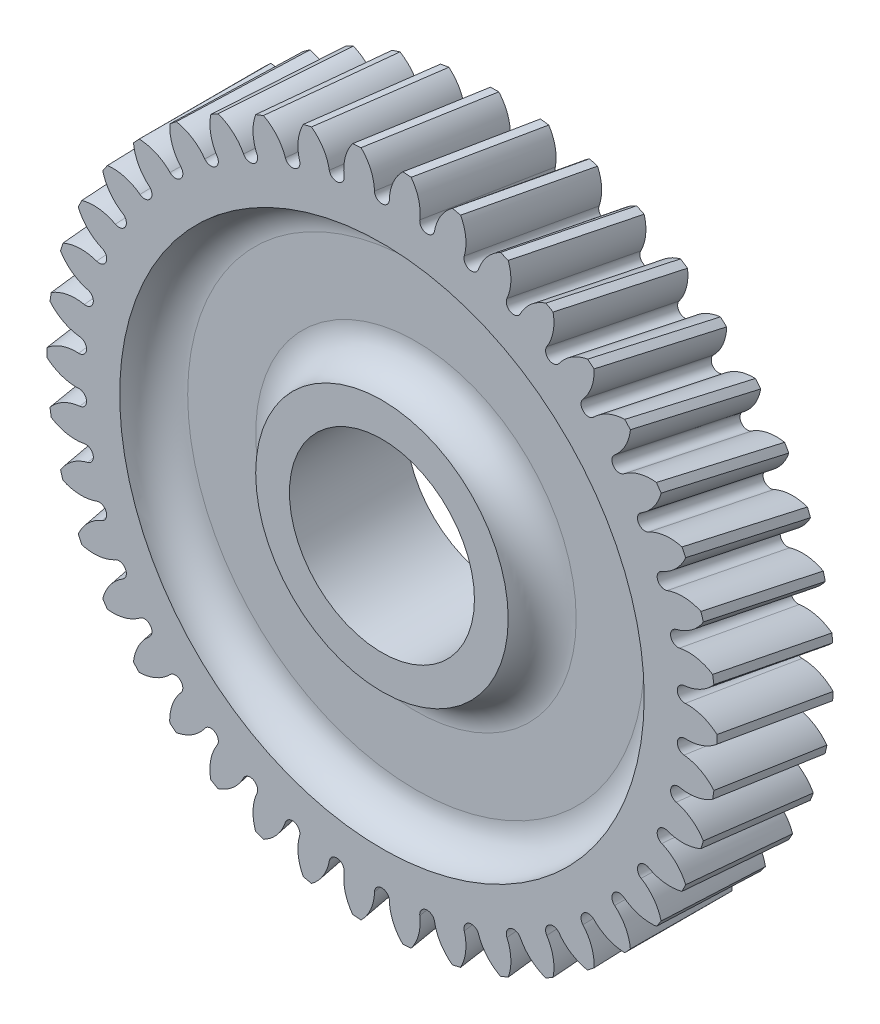
SolidWorks part; units mm, degrees
material "S355JR"
ref_plane "Front" through (0, 0, 0) normal (0, 0, 1) x (1, 0, 0)
ref_plane "Top" through (0, 0, 0) normal (0, 1, 0) x (1, 0, 0)
ref_plane "Right" through (0, 0, 0) normal (1, 0, 0) x (0, 0, -1)
sketch "Sketch1" plane through (0, 0, 0) normal (1, 0, 0) x (0, 0, -1)
  line L0 (6, 9.525) -> (-6, 9.525)
  line L1 (-6, 9.525) -> (-6, 13)
  line L2 (-2.5, 16.5) -> (-2.5, 23.5)
  line L3 (-6, 27) -> (-6, 34.5)
  line L4 (-6, 34.5) -> (6, 34.5)
  line L5 (0, 34.5) -> (0, 9.525) construction
  line L6 (6, 27) -> (6, 34.5)
  line L7 (2.5, 16.5) -> (2.5, 23.5)
  line L8 (6, 9.525) -> (6, 13)
  line L9 (0, 0) -> (28149.981, 0) construction
  arc A0 (-6, 13) -> (-2.5, 16.5) centre (-6, 16.5) ccw
  arc A1 (-2.5, 23.5) -> (-6, 27) centre (-6, 23.5) ccw
  arc A2 (2.5, 23.5) -> (6, 27) centre (6, 23.5) cw
  arc A3 (6, 13) -> (2.5, 16.5) centre (6, 16.5) cw
  dimension "D1" = 19.05
  dimension "D2" = 69
  dimension "D3" = 54
  dimension "D4" = 26
  dimension "D5" = 12
  dimension "D6" = 3.5
revolve "Revolve1" add sketch "Sketch1" angle 360 about L9
sketch "Sketch2" plane through (0, 0, 6) normal (0, 0, 1) x (1, 0, 0)
  line L0 (0, 0) -> (0, 48.7795) construction
  line L1 (-0.75, 30.4908) -> (0, 0) construction
  line L2 (-0.7687, 31.25) -> (-0.75, 30.4908) construction
  arc A0 (0.75, 30.4908) -> (-0.75, 30.4908) centre (0, 0) ccw construction
  circle A1 centre (0, 0) radius 34.5 construction
  arc A2 (2.15, 34.4329) -> (-2.15, 34.4329) centre (0, 0) ccw
  arc A6 (2.15, 34.4329) -> (0.7687, 31.25) centre (5.3884, 31.1364) ccw
  arc A7 (-0.7687, 31.25) -> (0.7687, 31.25) centre (0, 31.2689) ccw
  arc A8 (-2.15, 34.4329) -> (-0.7687, 31.25) centre (-5.3884, 31.1364) cw
  arc A9 (7.2579, 33.7279) -> (3.006, 34.3688) centre (0, 0) ccw construction
  arc A10 (7.2579, 33.7279) -> (5.4177, 30.7864) centre (9.9688, 29.9855) ccw construction
  arc A11 (3.8975, 31.0155) -> (5.4177, 30.7864) centre (4.6604, 30.9197) ccw construction
  arc A12 (3.006, 34.3688) -> (3.8975, 31.0155) centre (-0.6875, 31.5917) cw construction
  arc A13 (5.286, 30.0384) -> (3.8028, 30.262) centre (0, 0) ccw construction
  arc A14 (3.8975, 31.0155) -> (3.8028, 30.262) centre (0.6974, 31.0349) cw construction
  arc A15 (5.4177, 30.7864) -> (5.286, 30.0384) centre (7.5704, 30.022) ccw construction
  arc A16 (12.2038, 32.2695) -> (8.0948, 33.5369) centre (0, 0) ccw construction
  arc A17 (12.2038, 32.2695) -> (9.9456, 29.6351) centre (14.3266, 28.1648) ccw construction
  arc A18 (8.4766, 30.0882) -> (9.9456, 29.6351) centre (9.2167, 29.8797) ccw construction
  arc A19 (8.0948, 33.5369) -> (8.4766, 30.0882) centre (4.0286, 31.3413) cw construction
  arc A20 (9.704, 28.9151) -> (8.2706, 29.3572) centre (0, 0) ccw construction
  arc A21 (8.4766, 30.0882) -> (8.2706, 29.3572) centre (5.3152, 30.5844) cw construction
  arc A22 (9.9456, 29.6351) -> (9.704, 28.9151) centre (11.9604, 28.5584) ccw construction
  arc A23 (16.877, 30.0902) -> (13.0028, 31.9559) centre (0, 0) ccw construction
  arc A24 (16.877, 30.0902) -> (14.2514, 27.8218) centre (18.3643, 25.715) ccw construction
  arc A25 (12.8663, 28.4888) -> (14.2514, 27.8218) centre (13.5671, 28.1723) ccw construction
  arc A26 (13.0028, 31.9559) -> (12.8663, 28.4888) centre (8.6548, 30.3908) cw construction
  arc A27 (13.9052, 27.1458) -> (12.5537, 27.7967) centre (0, 0) ccw construction
  arc A28 (12.8663, 28.4888) -> (12.5537, 27.7967) centre (9.8142, 29.4506) cw construction
  arc A29 (14.2514, 27.8218) -> (13.9052, 27.1458) centre (16.0832, 26.4568) ccw construction
  arc A30 (21.1732, 27.2387) -> (17.6204, 29.661) centre (0, 0) ccw construction
  arc A31 (21.1732, 27.2387) -> (18.2389, 25.387) centre (21.9918, 22.6907) ccw construction
  arc A32 (16.9686, 26.253) -> (18.2389, 25.387) centre (17.6144, 25.8356) ccw construction
  arc A33 (17.6204, 29.661) -> (16.9686, 26.253) centre (13.0877, 28.7614) cw construction
  arc A34 (17.7957, 24.7702) -> (16.5564, 25.6152) centre (0, 0) ccw construction
  arc A35 (16.9686, 26.253) -> (16.5564, 25.6152) centre (14.0939, 27.6589) cw construction
  arc A36 (18.2389, 25.387) -> (17.7957, 24.7702) centre (19.8467, 23.7642) ccw construction
  arc A37 (24.9964, 23.7788) -> (21.8443, 26.7035) centre (0, 0) ccw construction
  arc A38 (24.9964, 23.7788) -> (21.8189, 22.385) centre (25.1281, 19.1596) ccw construction
  arc A39 (20.6919, 23.4307) -> (21.8189, 22.385) centre (21.2683, 22.9217) ccw construction
  arc A40 (21.8443, 26.7035) -> (20.6919, 23.4307) centre (17.2282, 26.4896) cw construction
  arc A41 (21.2888, 21.8412) -> (20.1892, 22.8615) centre (0, 0) ccw construction
  arc A42 (20.6919, 23.4307) -> (20.1892, 22.8615) centre (18.0589, 25.2494) cw construction
  arc A43 (21.8189, 22.385) -> (21.2888, 21.8412) centre (23.1669, 20.5408) ccw construction
  arc A44 (28.2613, 19.7877) -> (25.5803, 23.1495) centre (0, 0) ccw construction
  arc A45 (28.2613, 19.7877) -> (24.9115, 18.8831) centre (27.703, 15.2004) ccw construction
  arc A46 (23.953, 20.085) -> (24.9115, 18.8831) centre (24.447, 19.4958) ccw construction
  arc A47 (25.5803, 23.1495) -> (23.953, 20.085) centre (20.9838, 23.626) cw construction
  arc A48 (24.3063, 18.4243) -> (23.371, 19.5971) centre (0, 0) ccw construction
  arc A49 (23.953, 20.085) -> (23.371, 19.5971) centre (21.6204, 22.2758) cw construction
  arc A50 (24.9115, 18.8831) -> (24.3063, 18.4243) centre (25.9696, 16.8585) ccw construction
  arc A51 (30.8948, 15.3545) -> (28.7448, 19.0784) centre (0, 0) ccw construction
  arc A52 (30.8948, 15.3545) -> (27.4476, 14.9593) centre (29.6591, 10.9017) ccw construction
  arc A53 (26.679, 16.2907) -> (27.4476, 14.9593) centre (27.0797, 15.6345) ccw construction
  arc A54 (28.7448, 19.0784) -> (26.679, 16.2907) centre (24.2707, 20.2346) cw construction
  arc A55 (26.7808, 14.5959) -> (26.0308, 15.8949) centre (0, 0) ccw construction
  arc A56 (26.679, 16.2907) -> (26.0308, 15.8949) centre (24.6989, 18.8047) cw construction
  arc A57 (27.4476, 14.9593) -> (26.7808, 14.5959) centre (28.1922, 12.7997) ccw construction
  arc A58 (32.8382, 10.5784) -> (31.2672, 14.5811) centre (0, 0) ccw construction
  arc A59 (32.8382, 10.5784) -> (29.3706, 10.7014) centre (30.9526, 6.3595) ccw construction
  arc A60 (28.809, 12.1324) -> (29.3706, 10.7014) centre (29.1074, 11.4238) ccw construction
  arc A61 (31.2672, 14.5811) -> (28.809, 12.1324) centre (27.0154, 16.3913) cw construction
  arc A62 (28.6571, 10.4414) -> (28.1091, 11.8377) centre (0, 0) ccw construction
  arc A63 (28.809, 12.1324) -> (28.1091, 11.8377) centre (27.2258, 14.9135) cw construction
  arc A64 (29.3706, 10.7014) -> (28.6571, 10.4414) centre (29.785, 8.4549) ccw construction
  arc A65 (34.0481, 5.566) -> (33.0912, 9.7581) centre (0, 0) ccw construction
  arc A66 (34.0481, 5.566) -> (30.6375, 6.2044) centre (31.5547, 1.6752) ccw construction
  arc A67 (30.2955, 7.7032) -> (30.6375, 6.2044) centre (30.4849, 6.958) ccw construction
  arc A68 (33.0912, 9.7581) -> (30.2955, 7.7032) centre (29.1567, 12.1817) cw construction
  arc A69 (29.8932, 6.0536) -> (29.5594, 7.516) centre (0, 0) ccw construction
  arc A70 (30.2955, 7.7032) -> (29.5594, 7.516) centre (29.1444, 10.6891) cw construction
  arc A71 (30.6375, 6.2044) -> (29.8932, 6.0536) centre (30.7125, 3.9212) ccw construction
  arc A72 (34.4973, 0.4292) -> (34.176, 4.7172) centre (0, 0) ccw construction
  arc A73 (34.4973, 0.4292) -> (31.2201, 1.5688) centre (31.452, -3.0465) ccw construction
  arc A74 (31.1052, 3.1018) -> (31.2201, 1.5688) centre (31.1815, 2.3367) ccw construction
  arc A75 (34.176, 4.7172) -> (31.1052, 3.1018) centre (30.6466, 7.7001) cw construction
  arc A76 (30.4616, 1.5307) -> (30.3495, 3.0265) centre (0, 0) ccw construction
  arc A77 (31.1052, 3.1018) -> (30.3495, 3.0265) centre (30.412, 6.226) cw construction
  arc A78 (31.2201, 1.5688) -> (30.4616, 1.5307) centre (30.9539, -0.7) ccw construction
  arc A79 (34.176, -4.7172) -> (34.4973, -0.4292) centre (0, 0) ccw construction
  arc A80 (34.176, -4.7172) -> (31.1052, -3.1018) centre (30.6466, -7.7001) ccw construction
  arc A81 (31.2201, -1.5688) -> (31.1052, -3.1018) centre (31.1815, -2.3367) ccw construction
  arc A82 (34.4973, -0.4292) -> (31.2201, -1.5688) centre (31.452, 3.0465) cw construction
  arc A83 (30.3495, -3.0265) -> (30.4616, -1.5307) centre (0, 0) ccw construction
  arc A84 (31.2201, -1.5688) -> (30.4616, -1.5307) centre (31.0003, 1.6238) cw construction
  arc A85 (31.1052, -3.1018) -> (30.3495, -3.0265) centre (30.5038, -5.3057) ccw construction
  arc A86 (33.0912, -9.7581) -> (34.0481, -5.566) centre (0, 0) ccw construction
  arc A87 (33.0912, -9.7581) -> (30.2955, -7.7032) centre (29.1567, -12.1817) ccw construction
  arc A88 (30.6375, -6.2044) -> (30.2955, -7.7032) centre (30.4849, -6.958) ccw construction
  arc A89 (34.0481, -5.566) -> (30.6375, -6.2044) centre (31.5547, -1.6752) cw construction
  arc A90 (29.5594, -7.516) -> (29.8932, -6.0536) centre (0, 0) ccw construction
  arc A91 (30.6375, -6.2044) -> (29.8932, -6.0536) centre (30.896, -3.0147) cw construction
  arc A92 (30.2955, -7.7032) -> (29.5594, -7.516) centre (29.3723, -9.7927) ccw construction
  arc A93 (31.2672, -14.5811) -> (32.8382, -10.5784) centre (0, 0) ccw construction
  arc A94 (31.2672, -14.5811) -> (28.809, -12.1324) centre (27.0154, -16.3913) ccw construction
  arc A95 (29.3706, -10.7014) -> (28.809, -12.1324) centre (29.1074, -11.4238) ccw construction
  arc A96 (32.8382, -10.5784) -> (29.3706, -10.7014) centre (30.9526, -6.3595) cw construction
  arc A97 (28.1091, -11.8377) -> (28.6571, -10.4414) centre (0, 0) ccw construction
  arc A98 (29.3706, -10.7014) -> (28.6571, -10.4414) centre (30.1016, -7.5859) cw construction
  arc A99 (28.809, -12.1324) -> (28.1091, -11.8377) centre (27.5847, -14.0611) ccw construction
  arc A100 (28.7448, -19.0784) -> (30.8948, -15.3545) centre (0, 0) ccw construction
  arc A101 (28.7448, -19.0784) -> (26.679, -16.2907) centre (24.2707, -20.2346) ccw construction
  arc A102 (27.4476, -14.9593) -> (26.679, -16.2907) centre (27.0797, -15.6345) ccw construction
  arc A103 (30.8948, -15.3545) -> (27.4476, -14.9593) centre (29.6591, -10.9017) cw construction
  arc A104 (26.0308, -15.8949) -> (26.7808, -14.5959) centre (0, 0) ccw construction
  arc A105 (27.4476, -14.9593) -> (26.7808, -14.5959) centre (28.6348, -11.9876) cw construction
  arc A106 (26.679, -16.2907) -> (26.0308, -15.8949) centre (25.1809, -18.0153) ccw construction
  arc A107 (25.5803, -23.1495) -> (28.2613, -19.7877) centre (0, 0) ccw construction
  arc A108 (25.5803, -23.1495) -> (23.953, -20.085) centre (20.9838, -23.626) ccw construction
  arc A109 (24.9115, -18.8831) -> (23.953, -20.085) centre (24.447, -19.4958) ccw construction
  arc A110 (28.2613, -19.7877) -> (24.9115, -18.8831) centre (27.703, -15.2004) cw construction
  arc A111 (23.371, -19.5971) -> (24.3063, -18.4243) centre (0, 0) ccw construction
  arc A112 (24.9115, -18.8831) -> (24.3063, -18.4243) centre (26.5283, -16.1215) cw construction
  arc A113 (23.953, -20.085) -> (23.371, -19.5971) centre (22.2146, -21.5671) ccw construction
  arc A114 (21.8443, -26.7035) -> (24.9964, -23.7788) centre (0, 0) ccw construction
  arc A115 (21.8443, -26.7035) -> (20.6919, -23.4307) centre (17.2282, -26.4896) ccw construction
  arc A116 (21.8189, -22.385) -> (20.6919, -23.4307) centre (21.2683, -22.9217) ccw construction
  arc A117 (24.9964, -23.7788) -> (21.8189, -22.385) centre (25.1281, -19.1596) cw construction
  arc A118 (20.1892, -22.8615) -> (21.2888, -21.8412) centre (0, 0) ccw construction
  arc A119 (21.8189, -22.385) -> (21.2888, -21.8412) centre (23.8292, -19.8952) cw construction
  arc A120 (20.6919, -23.4307) -> (20.1892, -22.8615) centre (18.7521, -24.6372) ccw construction
  arc A121 (17.6204, -29.661) -> (21.1732, -27.2387) centre (0, 0) ccw construction
  arc A122 (17.6204, -29.661) -> (16.9686, -26.253) centre (13.0877, -28.7614) ccw construction
  arc A123 (18.2389, -25.387) -> (16.9686, -26.253) centre (17.6144, -25.8356) ccw construction
  arc A124 (21.1732, -27.2387) -> (18.2389, -25.387) centre (21.9918, -22.6907) cw construction
  arc A125 (16.5564, -25.6152) -> (17.7957, -24.7702) centre (0, 0) ccw construction
  arc A126 (18.2389, -25.387) -> (17.7957, -24.7702) centre (20.5979, -23.2246) cw construction
  arc A127 (16.9686, -26.253) -> (16.5564, -25.6152) centre (14.8707, -27.1569) ccw construction
  arc A128 (13.0028, -31.9559) -> (16.877, -30.0902) centre (0, 0) ccw construction
  arc A129 (13.0028, -31.9559) -> (12.8663, -28.4888) centre (8.6548, -30.3908) ccw construction
  arc A130 (14.2514, -27.8218) -> (12.8663, -28.4888) centre (13.5671, -28.1723) ccw construction
  arc A131 (16.877, -30.0902) -> (14.2514, -27.8218) centre (18.3643, -25.715) cw construction
  arc A132 (12.5537, -27.7967) -> (13.9052, -27.1458) centre (0, 0) ccw construction
  arc A133 (14.2514, -27.8218) -> (13.9052, -27.1458) centre (16.9064, -26.0352) cw construction
  arc A134 (12.8663, -28.4888) -> (12.5537, -27.7967) centre (10.6571, -29.0699) ccw construction
  arc A135 (8.0948, -33.5369) -> (12.2038, -32.2695) centre (0, 0) ccw construction
  arc A136 (8.0948, -33.5369) -> (8.4766, -30.0882) centre (4.0286, -31.3413) ccw construction
  arc A137 (9.9456, -29.6351) -> (8.4766, -30.0882) centre (9.2167, -29.8797) ccw construction
  arc A138 (12.2038, -32.2695) -> (9.9456, -29.6351) centre (14.3266, -28.1648) cw construction
  arc A139 (8.2706, -29.3572) -> (9.704, -28.9151) centre (0, 0) ccw construction
  arc A140 (9.9456, -29.6351) -> (9.704, -28.9151) centre (12.8372, -28.2641) cw construction
  arc A141 (8.4766, -30.0882) -> (8.2706, -29.3572) centre (6.2054, -30.3336) ccw construction
  arc A142 (3.006, -34.3688) -> (7.2579, -33.7279) centre (0, 0) ccw construction
  arc A143 (3.006, -34.3688) -> (3.8975, -31.0155) centre (-0.6875, -31.5917) ccw construction
  arc A144 (5.4177, -30.7864) -> (3.8975, -31.0155) centre (4.6604, -30.9197) ccw construction
  arc A145 (7.2579, -33.7279) -> (5.4177, -30.7864) centre (9.9688, -29.9855) cw construction
  arc A146 (3.8028, -30.262) -> (5.286, -30.0384) centre (0, 0) ccw construction
  arc A147 (5.4177, -30.7864) -> (5.286, -30.0384) centre (8.4813, -29.8617) cw construction
  arc A148 (3.8975, -31.0155) -> (3.8028, -30.262) centre (1.6151, -30.9196) ccw construction
  arc A149 (-2.15, -34.4329) -> (2.15, -34.4329) centre (0, 0) ccw construction
  arc A150 (-2.15, -34.4329) -> (-0.7687, -31.25) centre (-5.3884, -31.1364) ccw construction
  arc A151 (0.7687, -31.25) -> (-0.7687, -31.25) centre (0, -31.2689) ccw construction
  arc A152 (2.15, -34.4329) -> (0.7687, -31.25) centre (5.3884, -31.1364) cw construction
  arc A153 (-0.75, -30.4908) -> (0.75, -30.4908) centre (0, 0) ccw construction
  arc A154 (0.7687, -31.25) -> (0.75, -30.4908) centre (3.9359, -30.7923) cw construction
  arc A155 (-0.7687, -31.25) -> (-0.75, -30.4908) centre (-3.0113, -30.815) ccw construction
  arc A156 (-7.2579, -33.7279) -> (-3.006, -34.3688) centre (0, 0) ccw construction
  arc A157 (-7.2579, -33.7279) -> (-5.4177, -30.7864) centre (-9.9688, -29.9855) ccw construction
  arc A158 (-3.8975, -31.0155) -> (-5.4177, -30.7864) centre (-4.6604, -30.9197) ccw construction
  arc A159 (-3.006, -34.3688) -> (-3.8975, -31.0155) centre (0.6875, -31.5917) cw construction
  arc A160 (-5.286, -30.0384) -> (-3.8028, -30.262) centre (0, 0) ccw construction
  arc A161 (-3.8975, -31.0155) -> (-3.8028, -30.262) centre (-0.6974, -31.0349) cw construction
  arc A162 (-5.4177, -30.7864) -> (-5.286, -30.0384) centre (-7.5704, -30.022) ccw construction
  arc A163 (-12.2038, -32.2695) -> (-8.0948, -33.5369) centre (0, 0) ccw construction
  arc A164 (-12.2038, -32.2695) -> (-9.9456, -29.6351) centre (-14.3266, -28.1648) ccw construction
  arc A165 (-8.4766, -30.0882) -> (-9.9456, -29.6351) centre (-9.2167, -29.8797) ccw construction
  arc A166 (-8.0948, -33.5369) -> (-8.4766, -30.0882) centre (-4.0286, -31.3413) cw construction
  arc A167 (-9.704, -28.9151) -> (-8.2706, -29.3572) centre (0, 0) ccw construction
  arc A168 (-8.4766, -30.0882) -> (-8.2706, -29.3572) centre (-5.3152, -30.5844) cw construction
  arc A169 (-9.9456, -29.6351) -> (-9.704, -28.9151) centre (-11.9604, -28.5584) ccw construction
  arc A170 (-16.877, -30.0902) -> (-13.0028, -31.9559) centre (0, 0) ccw construction
  arc A171 (-16.877, -30.0902) -> (-14.2514, -27.8218) centre (-18.3643, -25.715) ccw construction
  arc A172 (-12.8663, -28.4888) -> (-14.2514, -27.8218) centre (-13.5671, -28.1723) ccw construction
  arc A173 (-13.0028, -31.9559) -> (-12.8663, -28.4888) centre (-8.6548, -30.3908) cw construction
  arc A174 (-13.9052, -27.1458) -> (-12.5537, -27.7967) centre (0, 0) ccw construction
  arc A175 (-12.8663, -28.4888) -> (-12.5537, -27.7967) centre (-9.8142, -29.4506) cw construction
  arc A176 (-14.2514, -27.8218) -> (-13.9052, -27.1458) centre (-16.0832, -26.4568) ccw construction
  arc A177 (-21.1732, -27.2387) -> (-17.6204, -29.661) centre (0, 0) ccw construction
  arc A178 (-21.1732, -27.2387) -> (-18.2389, -25.387) centre (-21.9918, -22.6907) ccw construction
  arc A179 (-16.9686, -26.253) -> (-18.2389, -25.387) centre (-17.6144, -25.8356) ccw construction
  arc A180 (-17.6204, -29.661) -> (-16.9686, -26.253) centre (-13.0877, -28.7614) cw construction
  arc A181 (-17.7957, -24.7702) -> (-16.5564, -25.6152) centre (0, 0) ccw construction
  arc A182 (-16.9686, -26.253) -> (-16.5564, -25.6152) centre (-14.0939, -27.6589) cw construction
  arc A183 (-18.2389, -25.387) -> (-17.7957, -24.7702) centre (-19.8467, -23.7642) ccw construction
  arc A184 (-24.9964, -23.7788) -> (-21.8443, -26.7035) centre (0, 0) ccw construction
  arc A185 (-24.9964, -23.7788) -> (-21.8189, -22.385) centre (-25.1281, -19.1596) ccw construction
  arc A186 (-20.6919, -23.4307) -> (-21.8189, -22.385) centre (-21.2683, -22.9217) ccw construction
  arc A187 (-21.8443, -26.7035) -> (-20.6919, -23.4307) centre (-17.2282, -26.4896) cw construction
  arc A188 (-21.2888, -21.8412) -> (-20.1892, -22.8615) centre (0, 0) ccw construction
  arc A189 (-20.6919, -23.4307) -> (-20.1892, -22.8615) centre (-18.0589, -25.2494) cw construction
  arc A190 (-21.8189, -22.385) -> (-21.2888, -21.8412) centre (-23.1669, -20.5408) ccw construction
  arc A191 (-28.2613, -19.7877) -> (-25.5803, -23.1495) centre (0, 0) ccw construction
  arc A192 (-28.2613, -19.7877) -> (-24.9115, -18.8831) centre (-27.703, -15.2004) ccw construction
  arc A193 (-23.953, -20.085) -> (-24.9115, -18.8831) centre (-24.447, -19.4958) ccw construction
  arc A194 (-25.5803, -23.1495) -> (-23.953, -20.085) centre (-20.9838, -23.626) cw construction
  arc A195 (-24.3063, -18.4243) -> (-23.371, -19.5971) centre (0, 0) ccw construction
  arc A196 (-23.953, -20.085) -> (-23.371, -19.5971) centre (-21.6204, -22.2758) cw construction
  arc A197 (-24.9115, -18.8831) -> (-24.3063, -18.4243) centre (-25.9696, -16.8585) ccw construction
  arc A198 (-30.8948, -15.3545) -> (-28.7448, -19.0784) centre (0, 0) ccw construction
  arc A199 (-30.8948, -15.3545) -> (-27.4476, -14.9593) centre (-29.6591, -10.9017) ccw construction
  arc A200 (-26.679, -16.2907) -> (-27.4476, -14.9593) centre (-27.0797, -15.6345) ccw construction
  arc A201 (-28.7448, -19.0784) -> (-26.679, -16.2907) centre (-24.2707, -20.2346) cw construction
  arc A202 (-26.7808, -14.5959) -> (-26.0308, -15.8949) centre (0, 0) ccw construction
  arc A203 (-26.679, -16.2907) -> (-26.0308, -15.8949) centre (-24.6989, -18.8047) cw construction
  arc A204 (-27.4476, -14.9593) -> (-26.7808, -14.5959) centre (-28.1922, -12.7997) ccw construction
  arc A205 (-32.8382, -10.5784) -> (-31.2672, -14.5811) centre (0, 0) ccw construction
  arc A206 (-32.8382, -10.5784) -> (-29.3706, -10.7014) centre (-30.9526, -6.3595) ccw construction
  arc A207 (-28.809, -12.1324) -> (-29.3706, -10.7014) centre (-29.1074, -11.4238) ccw construction
  arc A208 (-31.2672, -14.5811) -> (-28.809, -12.1324) centre (-27.0154, -16.3913) cw construction
  arc A209 (-28.6571, -10.4414) -> (-28.1091, -11.8377) centre (0, 0) ccw construction
  arc A210 (-28.809, -12.1324) -> (-28.1091, -11.8377) centre (-27.2258, -14.9135) cw construction
  arc A211 (-29.3706, -10.7014) -> (-28.6571, -10.4414) centre (-29.785, -8.4549) ccw construction
  arc A212 (-34.0481, -5.566) -> (-33.0912, -9.7581) centre (0, 0) ccw construction
  arc A213 (-34.0481, -5.566) -> (-30.6375, -6.2044) centre (-31.5547, -1.6752) ccw construction
  arc A214 (-30.2955, -7.7032) -> (-30.6375, -6.2044) centre (-30.4849, -6.958) ccw construction
  arc A215 (-33.0912, -9.7581) -> (-30.2955, -7.7032) centre (-29.1567, -12.1817) cw construction
  arc A216 (-29.8932, -6.0536) -> (-29.5594, -7.516) centre (0, 0) ccw construction
  arc A217 (-30.2955, -7.7032) -> (-29.5594, -7.516) centre (-29.1444, -10.6891) cw construction
  arc A218 (-30.6375, -6.2044) -> (-29.8932, -6.0536) centre (-30.7125, -3.9212) ccw construction
  arc A219 (-34.4973, -0.4292) -> (-34.176, -4.7172) centre (0, 0) ccw construction
  arc A220 (-34.4973, -0.4292) -> (-31.2201, -1.5688) centre (-31.452, 3.0465) ccw construction
  arc A221 (-31.1052, -3.1018) -> (-31.2201, -1.5688) centre (-31.1815, -2.3367) ccw construction
  arc A222 (-34.176, -4.7172) -> (-31.1052, -3.1018) centre (-30.6466, -7.7001) cw construction
  arc A223 (-30.4616, -1.5307) -> (-30.3495, -3.0265) centre (0, 0) ccw construction
  arc A224 (-31.1052, -3.1018) -> (-30.3495, -3.0265) centre (-30.412, -6.226) cw construction
  arc A225 (-31.2201, -1.5688) -> (-30.4616, -1.5307) centre (-30.9539, 0.7) ccw construction
  arc A226 (-34.176, 4.7172) -> (-34.4973, 0.4292) centre (0, 0) ccw construction
  arc A227 (-34.176, 4.7172) -> (-31.1052, 3.1018) centre (-30.6466, 7.7001) ccw construction
  arc A228 (-31.2201, 1.5688) -> (-31.1052, 3.1018) centre (-31.1815, 2.3367) ccw construction
  arc A229 (-34.4973, 0.4292) -> (-31.2201, 1.5688) centre (-31.452, -3.0465) cw construction
  arc A230 (-30.3495, 3.0265) -> (-30.4616, 1.5307) centre (0, 0) ccw construction
  arc A231 (-31.2201, 1.5688) -> (-30.4616, 1.5307) centre (-31.0003, -1.6238) cw construction
  arc A232 (-31.1052, 3.1018) -> (-30.3495, 3.0265) centre (-30.5038, 5.3057) ccw construction
  arc A233 (-33.0912, 9.7581) -> (-34.0481, 5.566) centre (0, 0) ccw construction
  arc A234 (-33.0912, 9.7581) -> (-30.2955, 7.7032) centre (-29.1567, 12.1817) ccw construction
  arc A235 (-30.6375, 6.2044) -> (-30.2955, 7.7032) centre (-30.4849, 6.958) ccw construction
  arc A236 (-34.0481, 5.566) -> (-30.6375, 6.2044) centre (-31.5547, 1.6752) cw construction
  arc A237 (-29.5594, 7.516) -> (-29.8932, 6.0536) centre (0, 0) ccw construction
  arc A238 (-30.6375, 6.2044) -> (-29.8932, 6.0536) centre (-30.896, 3.0147) cw construction
  arc A239 (-30.2955, 7.7032) -> (-29.5594, 7.516) centre (-29.3723, 9.7927) ccw construction
  arc A240 (-31.2672, 14.5811) -> (-32.8382, 10.5784) centre (0, 0) ccw construction
  arc A241 (-31.2672, 14.5811) -> (-28.809, 12.1324) centre (-27.0154, 16.3913) ccw construction
  arc A242 (-29.3706, 10.7014) -> (-28.809, 12.1324) centre (-29.1074, 11.4238) ccw construction
  arc A243 (-32.8382, 10.5784) -> (-29.3706, 10.7014) centre (-30.9526, 6.3595) cw construction
  arc A244 (-28.1091, 11.8377) -> (-28.6571, 10.4414) centre (0, 0) ccw construction
  arc A245 (-29.3706, 10.7014) -> (-28.6571, 10.4414) centre (-30.1016, 7.5859) cw construction
  arc A246 (-28.809, 12.1324) -> (-28.1091, 11.8377) centre (-27.5847, 14.0611) ccw construction
  arc A247 (-28.7448, 19.0784) -> (-30.8948, 15.3545) centre (0, 0) ccw construction
  arc A248 (-28.7448, 19.0784) -> (-26.679, 16.2907) centre (-24.2707, 20.2346) ccw construction
  arc A249 (-27.4476, 14.9593) -> (-26.679, 16.2907) centre (-27.0797, 15.6345) ccw construction
  arc A250 (-30.8948, 15.3545) -> (-27.4476, 14.9593) centre (-29.6591, 10.9017) cw construction
  arc A251 (-26.0308, 15.8949) -> (-26.7808, 14.5959) centre (0, 0) ccw construction
  arc A252 (-27.4476, 14.9593) -> (-26.7808, 14.5959) centre (-28.6348, 11.9876) cw construction
  arc A253 (-26.679, 16.2907) -> (-26.0308, 15.8949) centre (-25.1809, 18.0153) ccw construction
  arc A254 (-25.5803, 23.1495) -> (-28.2613, 19.7877) centre (0, 0) ccw construction
  arc A255 (-25.5803, 23.1495) -> (-23.953, 20.085) centre (-20.9838, 23.626) ccw construction
  arc A256 (-24.9115, 18.8831) -> (-23.953, 20.085) centre (-24.447, 19.4958) ccw construction
  arc A257 (-28.2613, 19.7877) -> (-24.9115, 18.8831) centre (-27.703, 15.2004) cw construction
  arc A258 (-23.371, 19.5971) -> (-24.3063, 18.4243) centre (0, 0) ccw construction
  arc A259 (-24.9115, 18.8831) -> (-24.3063, 18.4243) centre (-26.5283, 16.1215) cw construction
  arc A260 (-23.953, 20.085) -> (-23.371, 19.5971) centre (-22.2146, 21.5671) ccw construction
  arc A261 (-21.8443, 26.7035) -> (-24.9964, 23.7788) centre (0, 0) ccw construction
  arc A262 (-21.8443, 26.7035) -> (-20.6919, 23.4307) centre (-17.2282, 26.4896) ccw construction
  arc A263 (-21.8189, 22.385) -> (-20.6919, 23.4307) centre (-21.2683, 22.9217) ccw construction
  arc A264 (-24.9964, 23.7788) -> (-21.8189, 22.385) centre (-25.1281, 19.1596) cw construction
  arc A265 (-20.1892, 22.8615) -> (-21.2888, 21.8412) centre (0, 0) ccw construction
  arc A266 (-21.8189, 22.385) -> (-21.2888, 21.8412) centre (-23.8292, 19.8952) cw construction
  arc A267 (-20.6919, 23.4307) -> (-20.1892, 22.8615) centre (-18.7521, 24.6372) ccw construction
  arc A268 (-17.6204, 29.661) -> (-21.1732, 27.2387) centre (0, 0) ccw construction
  arc A269 (-17.6204, 29.661) -> (-16.9686, 26.253) centre (-13.0877, 28.7614) ccw construction
  arc A270 (-18.2389, 25.387) -> (-16.9686, 26.253) centre (-17.6144, 25.8356) ccw construction
  arc A271 (-21.1732, 27.2387) -> (-18.2389, 25.387) centre (-21.9918, 22.6907) cw construction
  arc A272 (-16.5564, 25.6152) -> (-17.7957, 24.7702) centre (0, 0) ccw construction
  arc A273 (-18.2389, 25.387) -> (-17.7957, 24.7702) centre (-20.5979, 23.2246) cw construction
  arc A274 (-16.9686, 26.253) -> (-16.5564, 25.6152) centre (-14.8707, 27.1569) ccw construction
  arc A275 (-13.0028, 31.9559) -> (-16.877, 30.0902) centre (0, 0) ccw construction
  arc A276 (-13.0028, 31.9559) -> (-12.8663, 28.4888) centre (-8.6548, 30.3908) ccw construction
  arc A277 (-14.2514, 27.8218) -> (-12.8663, 28.4888) centre (-13.5671, 28.1723) ccw construction
  arc A278 (-16.877, 30.0902) -> (-14.2514, 27.8218) centre (-18.3643, 25.715) cw construction
  arc A279 (-12.5537, 27.7967) -> (-13.9052, 27.1458) centre (0, 0) ccw construction
  arc A280 (-14.2514, 27.8218) -> (-13.9052, 27.1458) centre (-16.9064, 26.0352) cw construction
  arc A281 (-12.8663, 28.4888) -> (-12.5537, 27.7967) centre (-10.6571, 29.0699) ccw construction
  arc A282 (-8.0948, 33.5369) -> (-12.2038, 32.2695) centre (0, 0) ccw construction
  arc A283 (-8.0948, 33.5369) -> (-8.4766, 30.0882) centre (-4.0286, 31.3413) ccw construction
  arc A284 (-9.9456, 29.6351) -> (-8.4766, 30.0882) centre (-9.2167, 29.8797) ccw construction
  arc A285 (-12.2038, 32.2695) -> (-9.9456, 29.6351) centre (-14.3266, 28.1648) cw construction
  arc A286 (-8.2706, 29.3572) -> (-9.704, 28.9151) centre (0, 0) ccw construction
  arc A287 (-9.9456, 29.6351) -> (-9.704, 28.9151) centre (-12.8372, 28.2641) cw construction
  arc A288 (-8.4766, 30.0882) -> (-8.2706, 29.3572) centre (-6.2054, 30.3336) ccw construction
  arc A289 (-3.006, 34.3688) -> (-7.2579, 33.7279) centre (0, 0) ccw construction
  arc A290 (-3.006, 34.3688) -> (-3.8975, 31.0155) centre (0.6875, 31.5917) ccw construction
  arc A291 (-5.4177, 30.7864) -> (-3.8975, 31.0155) centre (-4.6604, 30.9197) ccw construction
  arc A292 (-7.2579, 33.7279) -> (-5.4177, 30.7864) centre (-9.9688, 29.9855) cw construction
  arc A293 (-3.8028, 30.262) -> (-5.286, 30.0384) centre (0, 0) ccw construction
  arc A294 (-5.4177, 30.7864) -> (-5.286, 30.0384) centre (-8.4813, 29.8617) cw construction
  arc A295 (-3.8975, 31.0155) -> (-3.8028, 30.262) centre (-1.6151, 30.9196) ccw construction
  point P9 (0, 0)
  point P469 (0, 0)
  dimension "D1" = 61
  dimension "D2" = 1.5
  dimension "D4" = 4.3
  dimension "D3" = 42
sketch "Sketch5" plane through (0, 0, 6) normal (0, 0, 1) x (1, 0, 0)
  circle A0 centre (0, 0) radius 34.5 construction
  circle A1 centre (0, 0) radius 34.5
curve "Helix/Spiral1" pitch 1193.2284 height 30 turns 0.0251
sweep "Cut-Sweep1" cut profiles "Sketch2" path "Helix/Spiral1" align with end faces yes
pattern_circular "CirPattern1" count 42 over 360 about axis through (0, 0, 0) along (0, 0, 1) of "Cut-Sweep1" reverse direction yes
